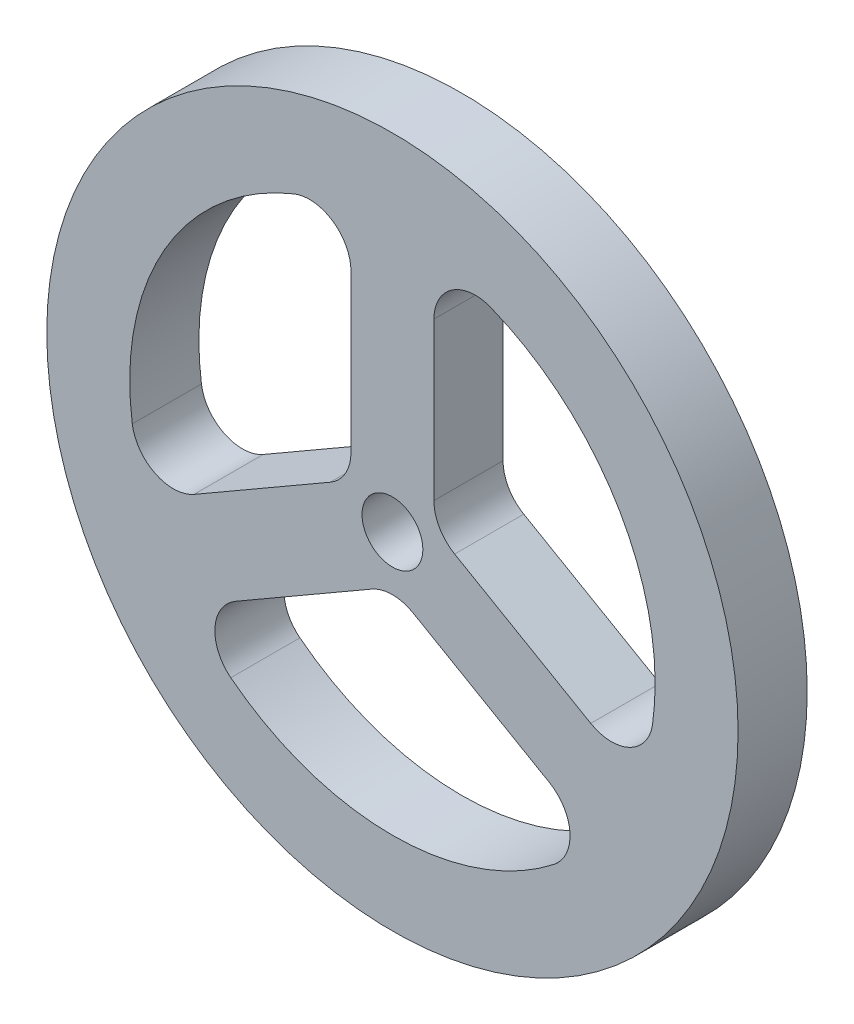
SolidWorks part; units mm, degrees
material "ABS"
ref_plane "Front Plane" through (0, 0, 0) normal (0, 0, 1) x (1, 0, 0)
ref_plane "Top Plane" through (0, 0, 0) normal (0, 1, 0) x (1, 0, 0)
ref_plane "Right Plane" through (0, 0, 0) normal (1, 0, 0) x (0, 0, -1)
sketch "Sketch1" plane through (0, 0, 0) normal (0, 0, 1) x (1, 0, 0)
  line L0 (0, 0) -> (0, 24.13) construction
  line L1 (0, 0) -> (20.8972, -12.065) construction
  line L2 (0, 0) -> (-20.8972, -12.065) construction
  line L3 (-3.81, 2.1997) -> (-22.8022, -8.7654)
  line L4 (0, -4.3994) -> (18.9922, -15.3646)
  line L5 (3.81, 2.1997) -> (3.81, 24.13)
  line L6 (0, -4.3994) -> (-18.9922, -15.3646)
  line L7 (3.81, 2.1997) -> (22.8022, -8.7654)
  line L8 (-3.81, 2.1997) -> (-3.81, 24.13)
  line L9 (1.905, 3.2996) -> (22.8022, -8.7654) construction
  line L10 (3.81, 0) -> (3.81, 24.13) construction
  line L11 (-1.905, 3.2996) -> (-22.8022, -8.7654) construction
  line L12 (-3.81, 0) -> (-3.81, 24.13) construction
  line L13 (-1.905, -3.2996) -> (18.9922, -15.3646) construction
  line L14 (1.905, -3.2996) -> (-18.9922, -15.3646) construction
  circle A0 centre (0, 0) radius 31.75
  circle A1 centre (0, 0) radius 2.794
  arc A3 (-18.7301, -15.2132) -> (18.7301, -15.2132) centre (0, 0) ccw
  arc A4 (22.5401, -8.6141) -> (3.81, 23.8273) centre (0, 0) ccw
  arc A5 (-3.81, 23.8273) -> (-22.5401, -8.6141) centre (0, 0) ccw
  point P12 (0, 0)
  dimension "D1" = 63.5
  dimension "D2" = 5.588
  dimension "D3" = 7.62
  dimension "D5" = 3.81
  dimension "D6" = 3.81
  dimension "D4" = 3
extrude "Boss-Extrude3" add sketch "Sketch1" along normal blind 6.35 contours A0 A5 L8 L3 A4 L7 L5 A3 L6 L4 A1 region at (-30.852, 0, 0)
fillet "Fillet1" radius 3.81 9 edges at (0, -4.3994, 3.175) (-18.7301, -15.2132, 3.175) (3.81, 23.8273, 3.175) (3.81, 2.1997, 3.175) (-22.5401, -8.6141, 3.175) (-3.81, 2.1997, 3.175) (-3.81, 23.8273, 3.175) (18.7301, -15.2132, 3.175) (22.5401, -8.6141, 3.175)
equation "\"rodThick\"= 0.085in"
equation "\"clear\"= 0.003in"
